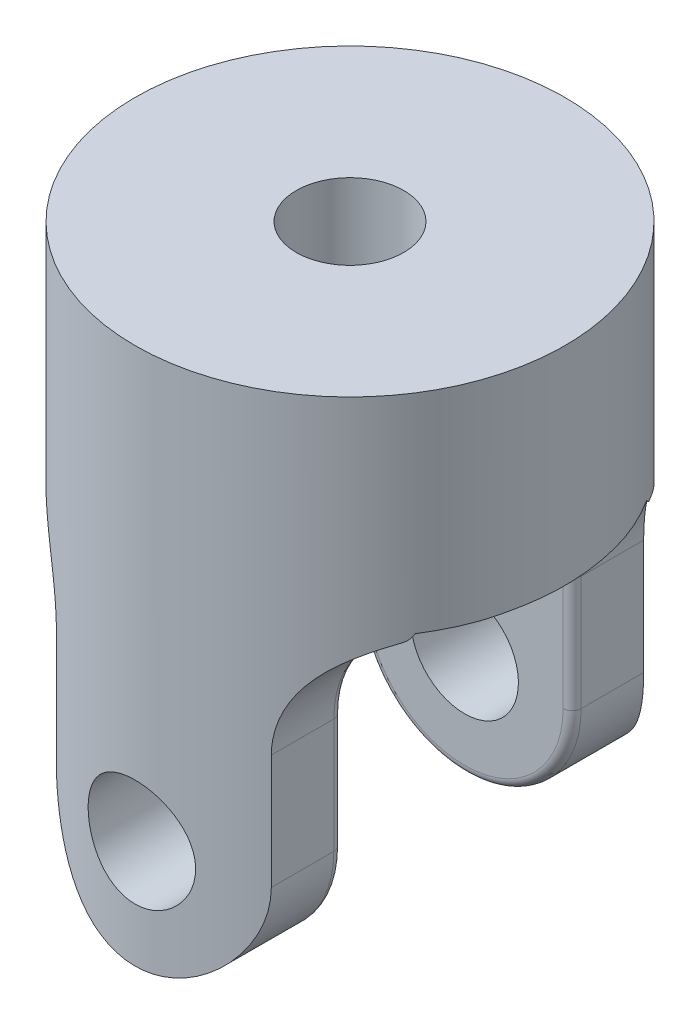
SolidWorks part; units mm, degrees
ref_plane "Front" through (0, 0, 0) normal (0, 0, 1) x (1, 0, 0)
ref_plane "Top" through (0, 0, 0) normal (0, 1, 0) x (-1, 0, 0)
ref_plane "Right" through (0, 0, 0) normal (1, 0, 0) x (0, 0, -1)
sketch "Sketch1" plane through (0, 0, 0) normal (0, 1, 0) x (-1, 0, 0)
  circle A0 centre (0, 0) radius 19.05
  dimension "D1" = 38.1
extrude "Base-Extrude" add sketch "Sketch1" along normal blind 47.625
sketch "Sketch2" plane through (0, 0, 0) normal (0, 0, 1) x (1, 0, 0)
  line L0 (0, 0) -> (0, 23.7435) construction
  line L1 (9.525, 9.525) -> (9.525, 19.685)
  line L2 (-9.525, 9.525) -> (-9.525, 19.685)
  line L3 (19.05, 29.21) -> (19.05, -1.3662)
  line L4 (19.05, -1.3662) -> (-19.05, -1.3662)
  line L5 (-19.05, -1.3662) -> (-19.05, 29.21)
  line L6 (19.05, 0) -> (-19.05, 0) construction
  arc A0 (-9.525, 9.525) -> (9.525, 9.525) centre (0, 9.525) ccw
  arc A1 (9.525, 19.685) -> (19.05, 29.21) centre (19.05, 19.685) cw
  arc A2 (-9.525, 19.685) -> (-19.05, 29.21) centre (-19.05, 19.685) ccw
  dimension "D3" = 9.525
  dimension "D1" = 38.1
  dimension "D2" = 19.05
  dimension "D4" = 29.21
extrude "Cut-Extrude1" cut sketch "Sketch2" against normal through all and the other way through all
sketch "Sketch8" plane through (0, 0, 0) normal (1, 0, 0) x (0, 0, -1)
  line L0 (-10.16, -7.4553) -> (10.16, -7.4553)
  line L1 (-10.16, -7.4553) -> (-10.16, 29.1452)
  line L2 (10.16, 29.1452) -> (-10.16, 29.1452)
  line L3 (10.16, 29.1452) -> (10.16, -7.4553)
  point P4 (0, 0)
  dimension "D1" = 10.16
  dimension "D2" = 20.32
extrude "Cut-Extrude5" cut sketch "Sketch8" against normal through all and the other way blind 47.625
fillet "Fillet1" radius 0.8001 10 edges at (11.3465, 25.287, -10.16) (9.525, 14.605, -10.16) (0, 0, -10.16) (-9.525, 14.605, -10.16) (-11.3465, 25.287, -10.16) (-11.3465, 25.287, 10.16) (-9.525, 14.605, 10.16) (0, 0, 10.16) (9.525, 14.605, 10.16) (11.3465, 25.287, 10.16)
sketch "Sketch11" plane through (0, 0, 0) normal (0, 0, 1) x (1, 0, 0)
  circle A0 centre (0, 9.525) radius 4.7625
  dimension "D1" = 9.525
extrude "Cut-Extrude6" cut sketch "Sketch11" against normal through all and the other way through all
sketch "Sketch12" plane through (0, 47.625, 0) normal (0, 1, 0) x (-1, 0, 0)
  circle A0 centre (0, 0) radius 4.7625
  dimension "D1" = 9.525
extrude "Cut-Extrude7" cut sketch "Sketch12" against normal through all
ref_axis "Axis1" through (0, 97.625, 0) along (0, -1, 0)
